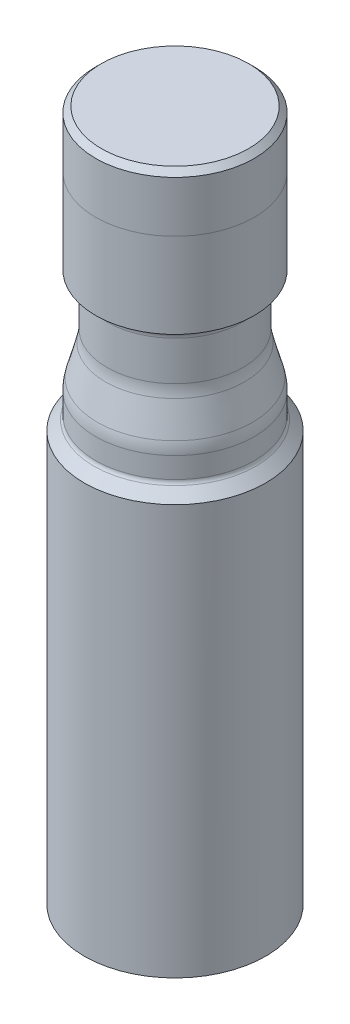
SolidWorks part; units mm, degrees
ref_plane "Piano frontale" through (0, 0, 0) normal (0, 0, 1) x (1, 0, 0)
ref_plane "Piano superiore" through (0, 0, 0) normal (0, 1, 0) x (1, 0, 0)
ref_plane "Piano destro" through (0, 0, 0) normal (1, 0, 0) x (0, 0, -1)
sketch "Sketch25" plane through (0, 0, 0) normal (0, 0, 1) x (1, 0, 0)
  line L0 (180, 60) -> (260, 60)
  line L2 (260, 421.6086) -> (250, 431.6086)
  line L3 (250, 431.6086) -> (250, 457.288)
  line L4 (250, 457.288) -> (240, 494.6086)
  line L5 (240, 494.6086) -> (240, 544.6086)
  line L6 (240, 544.6086) -> (250, 544.6086)
  line L7 (250, 544.6086) -> (250, 669.6086)
  line L8 (250, 669.6086) -> (180, 669.6086)
  line L9 (180, 669.6086) -> (180, 60)
  line L10 (260, 421.6086) -> (260, 60)
  dimension "D1" = 45
  dimension "D2" = 15
  dimension "D3" = 60
  dimension "D4" = 125
  dimension "D5" = 238
  dimension "D6" = 50
  dimension "D7" = 70
  dimension "D8" = 80
revolve "Revolve1" add sketch "Sketch25" angle 360 about L9
sketch "Sketch26" plane through (0, 669.6086, 0) normal (0, 1, 0) x (1, 0, 0)
  circle A0 centre (180, 0) radius 61.2
  dimension "D1" = 122.4
chamfer "Chamfer1" distance 5 angle 45 1 edges at (180, 669.6086, 70)
fillet "Fillet1" radius 10 1 edges at (180, 544.6086, 60)
fillet "Fillet2" radius 40 2 edges at (180, 494.6086, 60) (180, 457.288, 70)
fillet "Fillet3" radius 5 1 edges at (180, 431.6086, 70)
sketch "Sketch27" plane through (0, 0, 0) normal (0, 0, 1) x (1, 0, 0)
  line L0 (82.821, 619.6086) -> (297.279, 619.6086)
  dimension "D1" = 50
split line "Split Line1"
